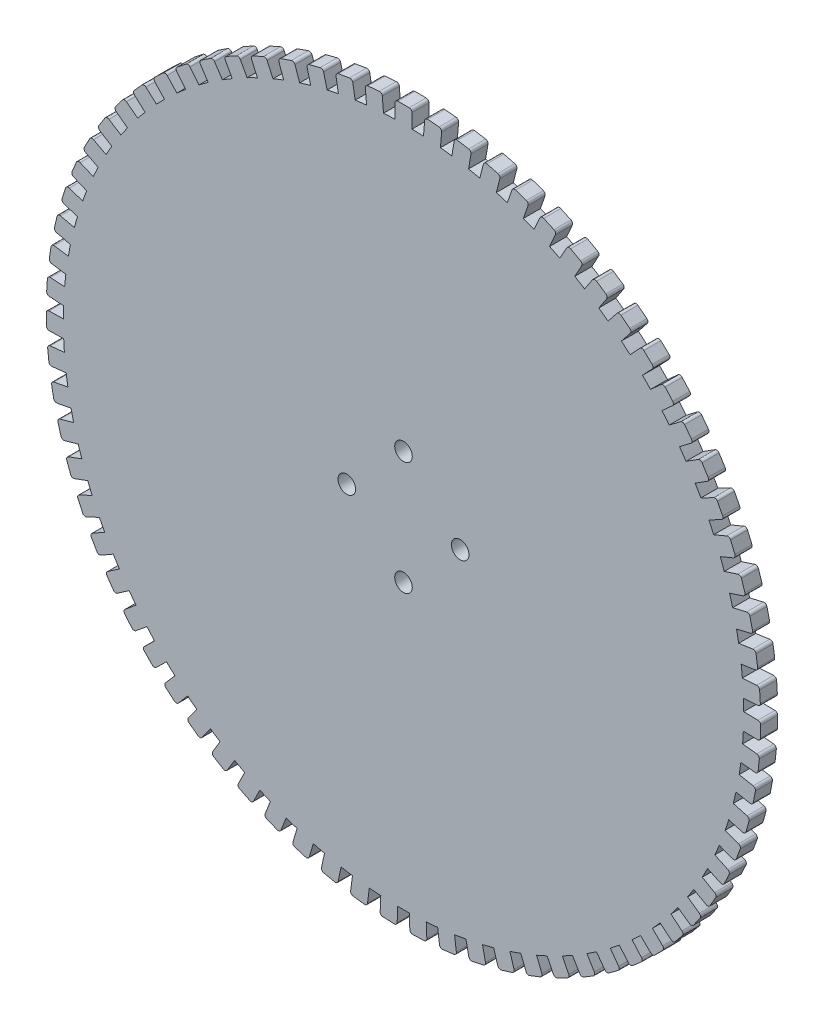
SolidWorks part; units mm, degrees
material "Pine"
ref_plane "Front Plane" through (0, 0, 0) normal (0, 0, 1) x (1, 0, 0)
ref_plane "Top Plane" through (0, 0, 0) normal (0, 1, 0) x (1, 0, 0)
ref_plane "Right Plane" through (0, 0, 0) normal (1, 0, 0) x (0, 0, -1)
sketch "Sketch2" plane through (0, 0, 0) normal (0, 0, 1) x (1, 0, 0)
  line L0 (0, 0) -> (0, 60) construction
  line L1 (-1.5, 60) -> (-1.5, 59.9812)
  line L2 (-1, 63) -> (1, 63)
  line L3 (-1.5, 62.5) -> (-1.5, 60)
  line L5 (1.5, 62.5) -> (1.5, 50)
  line L6 (0, 47) -> (0, 63) construction
  line L7 (-1.5, 60) -> (1.5, 60) construction
  line L8 (1.5, 50) -> (1.5, 59.9812)
  circle A0 centre (0, 0) radius 60
  circle A1 centre (0, 10) radius 1.55
  circle A2 centre (10, 0) radius 1.55
  circle A3 centre (0, -10) radius 1.55
  circle A4 centre (-10, 0) radius 1.55
  arc A5 (1.5, 62.5) -> (1, 63) centre (1, 62.5) ccw
  arc A6 (-1.5, 62.5) -> (-1, 63) centre (-1, 62.5) cw
  point P7 (11.4394, 6.2686)
  point P12 (0, 0)
  point P20 (0, 0)
  point P22 (1.5, 63)
  point P26 (-1.5, 63)
  dimension "D1" = 120
  dimension "D4" = 3.1
  dimension "D7" = 0.5
  dimension "D2" = 3
  dimension "D3" = 3
  dimension "D5" = 10
  dimension "D6" = 4
extrude "Boss-Extrude1" add sketch "Sketch2" along normal blind 3 contours A0 L3 region at (0, 0, 0)
extrude "Boss-Extrude2" add sketch "Sketch2<3>" along normal blind 3 contours A0 L8 L5 L2 L3 L1 region at (0, 61.4801, 0)
sketch "Sketch2<3>" plane through (0, 0, 0) normal (0, 0, 1) x (1, 0, 0) same geometry as "Sketch2"
pattern_circular "CirPattern2" count 75 over 360 about axis through (0, 0, 3) along (0, 0, 1) of "Boss-Extrude2"
sketch "Sketch3" plane through (0, 0, 0) normal (0, 0, -1) x (-1, 0, 0)
  point P0 (0, 0)
